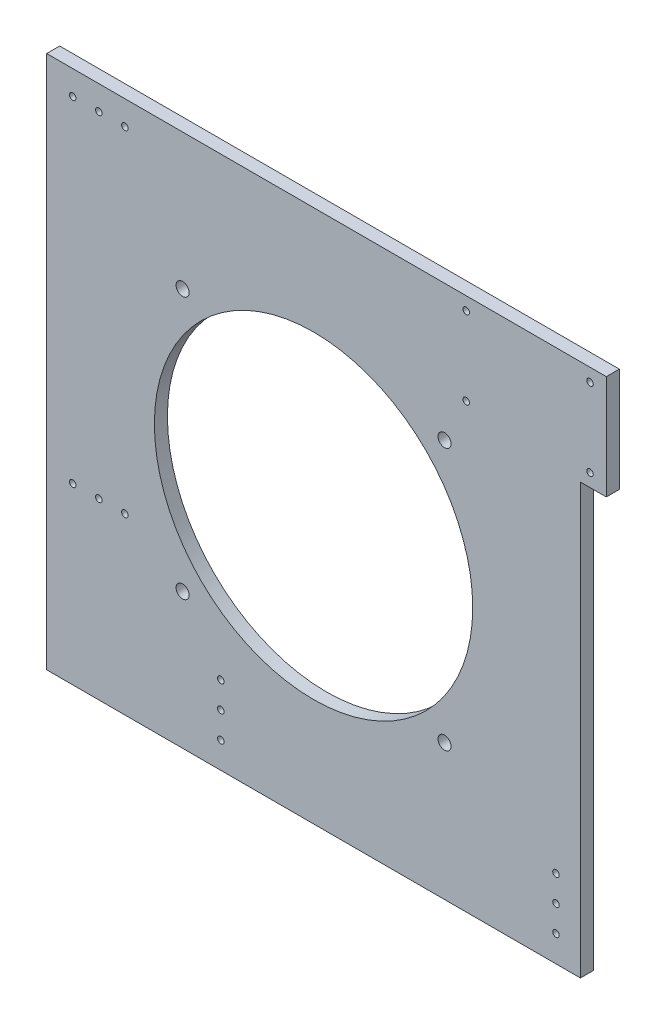
SolidWorks part; units mm, degrees
material "Perspex (TM) GS Acrylic Cast Sheet"
ref_plane "Front Plane" through (0, 0, 0) normal (0, 0, 1) x (1, 0, 0)
ref_plane "Top Plane" through (0, 0, 0) normal (0, 1, 0) x (1, 0, 0)
ref_plane "Right Plane" through (0, 0, 0) normal (1, 0, 0) x (0, 0, -1)
sketch "Sketch1" plane through (0, 0, 0) normal (0, 0, 1) x (1, 0, 0)
  line L1 (0, 0) -> (260.096, 0)
  line L2 (0, 0) -> (0, 260.096)
  line L3 (0, 260.096) -> (260.096, 260.096)
  line L4 (260.096, 0) -> (260.096, 260.096)
  dimension "D1" = 260.096
  dimension "D2" = 260.096
extrude "Boss-Extrude1" add sketch "Sketch1" along normal blind 6.35 contours L3 L4 L1 L2
sketch "Sketch2" plane through (0, 0, 6.35) normal (0, 0, 1) x (1, 0, 0)
  line L0 (-199790.1854, 50.896) -> (200353.3915, 50.896) construction
  line L1 (-199790.1854, 50.896) -> (200353.3915, 50.896) construction
  line L2 (130.048, 0) -> (130.048, 260.096) construction
  line L3 (0, 0) -> (260.096, 0) construction
  line L4 (0, 260.096) -> (260.096, 260.096) construction
  line L5 (260.096, 130.048) -> (0, 130.048) construction
  line L6 (0, 0) -> (0, 260.096) construction
  line L7 (260.096, 0) -> (260.096, 260.096) construction
  circle A0 centre (130.048, 130.048) radius 79.152 construction
  circle A1 centre (130.048, 130.048) radius 77.5645
  dimension "D1" = 1.5875
extrude "Cut-Extrude1" cut sketch "Sketch2" against normal through all
sketch "Sketch3" plane through (0, 0, 0) normal (0, 0, -1) x (-1, 0, 0)
  line L0 (-272.7, 209.296) -> (-272.7, 260.096) construction
  line L1 (-272.7, 209.296) -> (-272.7, 260.096)
  line L2 (-272.7, 209.296) -> (-260.096, 209.296)
  line L3 (-260.096, 0) -> (-260.096, 260.096) construction
  line L4 (-260.096, 209.296) -> (-260.096, 260.096)
  line L5 (-260.096, 260.096) -> (-272.7, 260.096)
extrude "Boss-Extrude2" add sketch "Sketch3" against normal up to surface (6.35 mm away) up to face at (207.6125, 130.048, 6.35)
sketch "Sketch5" plane through (0, 0, 6.35) normal (0, 0, 1) x (1, 0, 0)
  line L0 (260.096, 0) -> (0, 260.096) construction
  line L1 (260.096, 260.096) -> (0, 0) construction
  line L2 (0, 260.096) -> (272.7, 260.096) construction
  line L3 (260.096, 209.296) -> (260.096, 260.096) construction
  line L6 (0, 130.048) -> (260.096, 130.048) construction
  line L9 (0, 0) -> (0, 260.096) construction
  line L10 (260.096, 0) -> (260.096, 209.296) construction
  line L11 (0, 0) -> (260.096, 0) construction
  circle A0 centre (193.8746, 66.2214) radius 3.175
  circle A1 centre (130.048, 130.048) radius 77.5645 construction
  circle A2 centre (66.2214, 193.8746) radius 3.175
  circle A3 centre (193.8746, 193.8746) radius 3.175
  circle A4 centre (66.2214, 66.2214) radius 3.175
  point P3 (184.8944, 75.2016)
  dimension "D2" = 6.35
  dimension "D1" = 12.7
extrude "Cut-Extrude2" cut sketch "Sketch5" against normal through all
sketch "Sketch6" plane through (0, 0, 6.35) normal (0, 0, 1) x (1, 0, 0)
  circle A0 centre (264.7625, 253.746) radius 1.5875 construction
  circle A1 centre (264.7625, 215.646) radius 1.5875 construction
  circle A2 centre (204.4375, 253.746) radius 1.5875 construction
  circle A3 centre (204.4375, 215.646) radius 1.5875 construction
  circle A4 centre (264.7625, 253.746) radius 1.5875
  circle A5 centre (264.7625, 215.646) radius 1.5875
  circle A6 centre (204.4375, 253.746) radius 1.5875
  circle A7 centre (204.4375, 215.646) radius 1.5875
extrude "Cut-Extrude3" cut sketch "Sketch6" against normal through all
sketch "Sketch7" plane through (0, 0, 6.35) normal (0, 0, 1) x (1, 0, 0)
  circle A0 centre (248.189, 12.796) radius 1.5875 construction
  circle A1 centre (248.189, 25.496) radius 1.5875 construction
  circle A2 centre (248.189, 38.196) radius 1.5875 construction
  circle A3 centre (248.189, 12.796) radius 1.5875
  circle A4 centre (248.189, 25.496) radius 1.5875
  circle A5 centre (248.189, 38.196) radius 1.5875
  circle A6 centre (84.867, 12.796) radius 1.5875 construction
  circle A7 centre (84.867, 25.496) radius 1.5875 construction
  circle A8 centre (84.867, 38.196) radius 1.5875 construction
  circle A9 centre (12.7, 84.963) radius 1.5875 construction
  circle A10 centre (25.4, 84.963) radius 1.5875 construction
  circle A11 centre (38.1, 84.963) radius 1.5875 construction
  circle A12 centre (38.1, 248.285) radius 1.5875 construction
  circle A13 centre (25.4, 248.285) radius 1.5875 construction
  circle A14 centre (12.7, 248.285) radius 1.5875 construction
  circle A15 centre (84.867, 12.796) radius 1.5875
  circle A16 centre (84.867, 25.496) radius 1.5875
  circle A17 centre (84.867, 38.196) radius 1.5875
  circle A18 centre (12.7, 84.963) radius 1.5875
  circle A19 centre (25.4, 84.963) radius 1.5875
  circle A20 centre (38.1, 84.963) radius 1.5875
  circle A21 centre (38.1, 248.285) radius 1.5875
  circle A22 centre (25.4, 248.285) radius 1.5875
  circle A23 centre (12.7, 248.285) radius 1.5875
extrude "Cut-Extrude4" cut sketch "Sketch7" against normal through all
